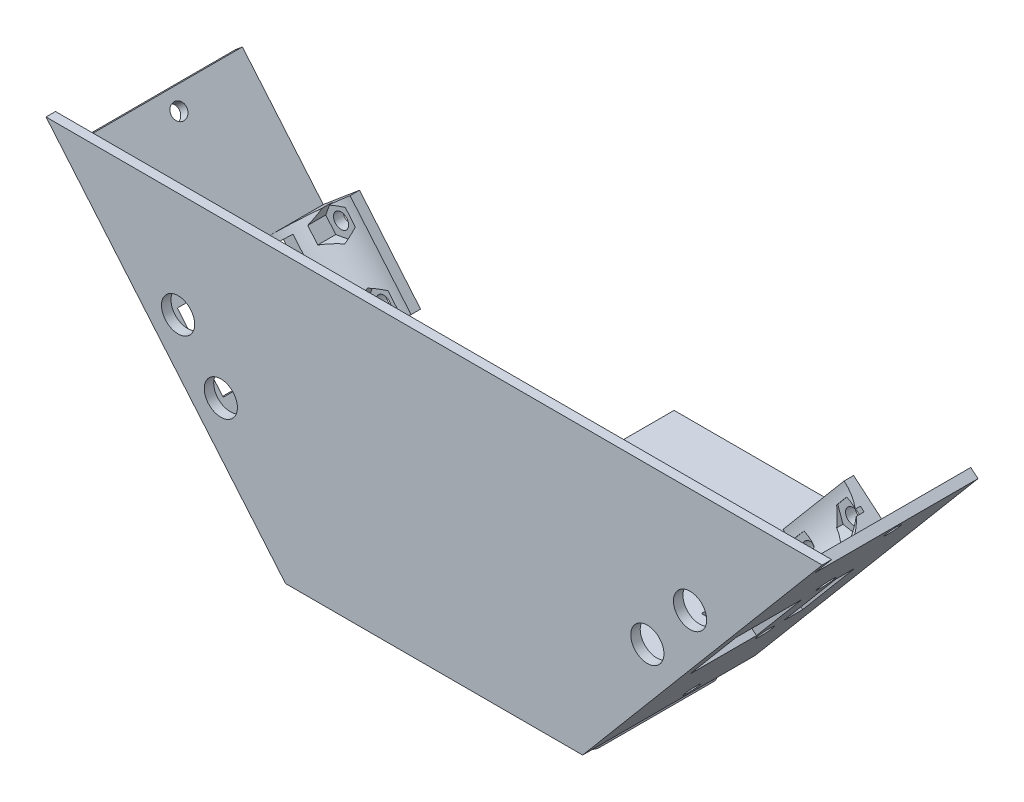
SolidWorks part; units mm, degrees
ref_plane "Front Plane" through (0, 0, 0) normal (0, 0, 1) x (1, 0, 0)
ref_plane "Top Plane" through (0, 0, 0) normal (0, 1, 0) x (1, 0, 0)
ref_plane "Right Plane" through (0, 0, 0) normal (1, 0, 0) x (0, 0, -1)
sketch "Sketch1" plane through (0, 0, 0) normal (0, 0, 1) x (1, 0, 0)
  line L0 (31.35, -1) -> (78.3808, 54.8311)
  line L1 (-31.35, -1) -> (31.35, -1)
  line L3 (-30.4197, 1) -> (30.4197, 1)
  line L5 (0, 0) -> (0, 17.9278) construction
  line L6 (-76.8512, 56.1196) -> (-30.4197, 1)
  line L7 (78.3808, 54.8311) -> (76.8512, 56.1196)
  line L8 (76.8512, 56.1196) -> (30.4197, 1)
  line L9 (-78.3808, 54.8311) -> (-76.8512, 56.1196)
  line L10 (30.4197, 1) -> (-30.4197, 1)
  line L11 (-31.35, -1) -> (-78.3808, 54.8311)
  point P0 (0, 0)
  dimension "D1" = 62.7
  dimension "D2" = 73
  dimension "D3" = 130.11
  dimension "D4" = 2
extrude "Boss-Extrude1" add sketch "Sketch1" along normal blind 31.4 contours L11 L1 L0 L7 L8 L10 L3 L6 L9 region at (0, 0.6684, 0)
sketch "Sketch2" plane through (0, 0, 0) normal (0, 0, -1) x (-1, 0, 0)
  line L0 (46.8932, 20.556) -> (39.2451, 26.9985)
  line L1 (76.8512, 56.1196) -> (30.4197, 1) construction
  line L2 (39.2451, 26.9985) -> (52.1302, 42.2947)
  line L3 (52.1302, 42.2947) -> (59.7783, 35.8521)
  line L4 (59.7783, 35.8521) -> (46.8932, 20.556)
  line L5 (78.3808, 54.8311) -> (76.8512, 56.1196) construction
  line L6 (0, 1) -> (0, 26.9985) construction
  line L7 (30.4197, 1) -> (-30.4197, 1) construction
  line L8 (-52.1302, 42.2947) -> (-59.7783, 35.8521)
  line L9 (-39.2451, 26.9985) -> (-52.1302, 42.2947)
  line L10 (-46.8932, 20.556) -> (-39.2451, 26.9985)
  line L11 (-59.7783, 35.8521) -> (-46.8932, 20.556)
  circle A0 centre (54.0215, 36.779) radius 1.6
  circle A1 centre (45.0019, 26.0717) radius 1.6014
  circle A2 centre (-45.0019, 26.0717) radius 1.6014
  circle A3 centre (-54.0215, 36.779) radius 1.6
  dimension "D4" = 3.2
  dimension "D5" = 3.2027
  dimension "D1" = 26.5
  dimension "D2" = 20
  dimension "D3" = 10
  dimension "D6" = 14
  dimension "D7" = 3
extrude "Boss-Extrude2" add sketch "Sketch2" against normal blind 2
fillet "Fillet1" radius 10 2 edges at (-53.3358, 28.204, 2) (53.3358, 28.204, 2)
sketch "Sketch3" plane through (0, 0, 0) normal (0, 0, -1) x (-1, 0, 0)
  line L1 (-50.7817, 37.3567) -> (-52.9019, 39.8736)
  line L2 (-52.9019, 39.8736) -> (-56.1417, 39.2959)
  line L3 (-56.1417, 39.2959) -> (-57.2613, 36.2013)
  line L4 (-57.2613, 36.2013) -> (-55.1411, 33.6844)
  line L5 (-55.1411, 33.6844) -> (-51.9013, 34.2621)
  line L6 (-51.9013, 34.2621) -> (-50.7817, 37.3567)
  line L7 (0, 0) -> (0, 47.8855) construction
  line L8 (-42.8817, 23.5548) -> (-41.7621, 26.6493)
  line L9 (-41.7621, 26.6493) -> (-43.8823, 29.1663)
  line L10 (-43.8823, 29.1663) -> (-47.1221, 28.5886)
  line L11 (-47.1221, 28.5886) -> (-48.2417, 25.494)
  line L12 (-48.2417, 25.494) -> (-46.1215, 22.9771)
  line L13 (-46.1215, 22.9771) -> (-42.8817, 23.5548)
  line L14 (46.1215, 22.9771) -> (42.8817, 23.5548)
  line L15 (48.2417, 25.494) -> (46.1215, 22.9771)
  line L16 (47.1221, 28.5886) -> (48.2417, 25.494)
  line L17 (43.8823, 29.1663) -> (47.1221, 28.5886)
  line L18 (41.7621, 26.6493) -> (43.8823, 29.1663)
  line L19 (42.8817, 23.5548) -> (41.7621, 26.6493)
  line L20 (51.9013, 34.2621) -> (50.7817, 37.3567)
  line L21 (55.1411, 33.6844) -> (51.9013, 34.2621)
  line L22 (57.2613, 36.2013) -> (55.1411, 33.6844)
  line L23 (56.1417, 39.2959) -> (57.2613, 36.2013)
  line L24 (52.9019, 39.8736) -> (56.1417, 39.2959)
  line L25 (50.7817, 37.3567) -> (52.9019, 39.8736)
  line L26 (-39.2451, 26.9985) -> (-52.1302, 42.2947) construction
  circle A0 centre (-54.0215, 36.779) radius 2.85 construction
  circle A1 centre (-45.0019, 26.0717) radius 2.85 construction
  dimension "D1" = 5.7
  dimension "D2" = 5.7
extrude "Cut-Extrude1" cut sketch "Sketch3" against normal blind 12 from offset 2 offset against normal yes
sketch "Sketch4" plane through (18.8304, -15.8623, 0) normal (0.7648, -0.6443, 0) x (0, 0, -1)
  line L0 (-31.4, 92.4327) -> (0, 92.4327) construction
  circle A0 centre (-15.7, 88.8327) radius 1.6
  circle A1 centre (-15.7, 23.0327) radius 1.6
  dimension "D1" = 3.2
  dimension "D3" = 3.2
  dimension "D2" = 65.8
  dimension "D4" = 3.6
extrude "Cut-Extrude2" cut sketch "Sketch4" against normal blind 2
mirror "Mirror1" about plane through (0, 0, 0) normal (1, 0, 0) of "Cut-Extrude2"
sketch "Sketch5" plane through (0, -1, 0) normal (0, -1, 0) x (1, 0, 0)
  line L0 (31.35, 31.4) -> (31.35, 0) construction
  line L1 (-24.25, 22.95) -> (-19.818, 22.95)
  line L2 (-24.25, 22.95) -> (-24.25, 8.45)
  line L3 (-24.25, 8.45) -> (-19.818, 8.45)
  line L4 (24.25, 22.95) -> (24.25, 8.45)
  line L5 (-24.25, 22.95) -> (-19.818, 21.625) construction
  line L6 (19.954, 22.95) -> (24.25, 22.95)
  line L7 (19.818, 26.15) -> (19.954, 26.15)
  line L8 (-19.818, 27.65) -> (-6, 27.65)
  line L9 (-19.818, 27.65) -> (-19.818, 22.95)
  line L10 (-19.818, 3.75) -> (19.818, 3.75)
  line L11 (19.818, 27.65) -> (19.818, 26.15)
  line L12 (6, 27.65) -> (19.818, 27.65)
  line L13 (-19.818, 3.75) -> (-12.0235, 8.45) construction
  line L14 (19.954, 26.15) -> (19.954, 22.95)
  line L15 (6, 27.65) -> (6, 29.65)
  line L16 (-26.25, 29.65) -> (-6, 29.65)
  line L17 (-26.25, 29.65) -> (-26.25, 1.75)
  line L18 (-26.25, 1.75) -> (26.25, 1.75)
  line L19 (26.25, 29.65) -> (26.25, 1.75)
  line L20 (-26.25, 29.65) -> (-19.818, 26.2319) construction
  line L21 (-26.25, 1.75) -> (-19.818, 5.1681) construction
  line L22 (-6, 27.65) -> (-6, 29.65)
  line L23 (-19.818, 8.45) -> (-19.818, 3.75)
  line L24 (6, 29.65) -> (26.25, 29.65)
  line L26 (19.818, 5.1681) -> (26.25, 1.75) construction
  line L28 (12.0235, 22.95) -> (19.818, 27.65) construction
  line L29 (13.6425, 22.95) -> (26.25, 29.65) construction
  line L31 (19.818, 8.45) -> (24.25, 8.45)
  line L32 (19.818, 8.45) -> (19.818, 3.75)
  point P0 (0, 15.7)
  point P10 (31.35, 15.7)
  point P11 (0, 15.7)
  point P16 (0, 15.7)
  dimension "D1" = 48.5
  dimension "D2" = 14.5
  dimension "D3" = 39.636
  dimension "D4" = 23.9
  dimension "D5" = 1.5
  dimension "D6" = 0.136
  dimension "D7" = 2
  dimension "D8" = 2
  dimension "D10" = 12
extrude "Boss-Extrude3" add sketch "Sketch5" along normal blind 4.9
sketch "Sketch6" plane through (0, -5.9, 0) normal (0, -1, 0) x (1, 0, 0)
  line L0 (-6, 29.65) -> (-26.25, 29.65)
  line L1 (-26.25, 29.65) -> (-26.25, 1.75)
  line L2 (-26.25, 1.75) -> (26.25, 1.75)
  line L3 (26.25, 1.75) -> (26.25, 29.65)
  line L4 (26.25, 29.65) -> (6, 29.65)
  line L5 (6, 29.65) -> (6, 27.65)
  line L6 (6, 27.65) -> (24.25, 27.65)
  line L7 (24.25, 27.65) -> (24.25, 3.75)
  line L8 (24.25, 3.75) -> (-24.25, 3.75)
  line L9 (-24.25, 3.75) -> (-24.25, 27.65)
  line L10 (-24.25, 27.65) -> (-6, 27.65)
  line L11 (-19.818, 27.65) -> (-6, 27.65) construction
  line L12 (-19.818, 27.65) -> (-6, 27.65) construction
  line L13 (-6, 27.65) -> (-6, 29.65)
extrude "Boss-Extrude4" add sketch "Sketch6" along normal blind 0.6
fillet "Fillet2" radius 2 4 edges at (26.25, -3.75, 29.65) (26.25, -3.75, 1.75) (-26.25, -3.75, 1.75) (-26.25, -3.75, 29.65)
fillet "Fillet3" radius 4 8 edges at (-15.125, -1, 29.65) (-25.6642, -1, 29.0642) (-26.25, -1, 15.7) (-25.6642, -1, 2.3358) (15.125, -1, 29.65) (25.6642, -1, 29.0642) (26.25, -1, 15.7) (25.6642, -1, 2.3358)
sketch "Sketch7" plane through (0, -6.5, 0) normal (0, -1, 0) x (1, 0, 0)
  line L0 (-24.25, 8.45) -> (-24.25, 22.95) construction
  line L1 (-18.25, 13.8577) -> (-30.25, 13.8577)
  line L2 (-18.25, 13.8577) -> (-18.25, 17.5423)
  line L3 (-18.25, 17.5423) -> (-30.25, 17.5423)
  line L4 (-30.25, 13.8577) -> (-30.25, 17.5423)
  line L5 (-18.25, 13.8577) -> (-30.25, 17.5423) construction
  line L6 (-18.25, 17.5423) -> (-30.25, 13.8577) construction
  line L7 (-30.25, 3.75) -> (-30.25, 27.65) construction
  point P0 (-24.25, 15.7)
extrude "Cut-Extrude3" cut sketch "Sketch7" against normal blind 2
sketch "Sketch8" plane through (0, 0, 0) normal (0, 0, -1) x (-1, 0, 0)
  line L0 (30.4197, 1) -> (-30.4197, 1) construction
  line L1 (-20, -1) -> (20, -1)
  line L2 (-20, -1) -> (-20, 1)
  line L3 (-20, 1) -> (20, 1)
  line L4 (20, -1) -> (20, 1)
  line L5 (-20, -1) -> (20, 1) construction
  line L6 (-20, 1) -> (20, -1) construction
  point P0 (0, 0)
  dimension "D1" = 40
extrude "Boss-Extrude5" add sketch "Sketch8" along normal blind 40
sketch "Sketch9" plane through (0, -1, 0) normal (0, -1, 0) x (1, 0, 0)
  line L0 (20, -40) -> (-20, -40) construction
  line L1 (-12.75, -7.75) -> (12.75, -7.75)
  line L2 (-12.75, -7.75) -> (-12.75, -32.25)
  line L3 (-12.75, -32.25) -> (12.75, -32.25)
  line L4 (12.75, -7.75) -> (12.75, -32.25)
  line L5 (-12.75, -7.75) -> (12.75, -32.25) construction
  line L6 (-12.75, -32.25) -> (12.75, -7.75) construction
  line L7 (-20, -40) -> (-20, 0) construction
  line L8 (-14.75, -5.75) -> (-14.75, -34.25)
  line L9 (-14.75, -34.25) -> (14.75, -34.25)
  line L10 (14.75, -5.75) -> (14.75, -34.25)
  line L11 (-14.75, -5.75) -> (14.75, -5.75)
  line L12 (-12.75, -11.5) -> (9.4027, -11.5) construction
  line L13 (0, -20) -> (29.1321, -20) construction
  circle A8 centre (10.5, -17.75) radius 1.1
  circle A9 centre (10.5, -17.75) radius 2.1
  circle A10 centre (-10.5, -17.75) radius 1.1
  circle A11 centre (-10.5, -17.75) radius 2.1
  circle A12 centre (-10.5, -29.75) radius 1.1
  circle A13 centre (-10.5, -29.75) radius 2.1
  circle A14 centre (10.5, -29.75) radius 1.1
  circle A15 centre (10.5, -29.75) radius 2.1
  point P0 (0, -20)
  point P8 (0, -40)
  point P10 (-20, -20)
  dimension "D5" = 2.25
  dimension "D7" = 2.2
  dimension "D8" = 2.2
  dimension "D1" = 25.5
  dimension "D2" = 24.5
  dimension "D4" = 2.5
  dimension "D6" = 2.25
  dimension "D9" = 12
  dimension "D3" = 2
extrude "Boss-Extrude6" add sketch "Sketch9" along normal blind 4 contours L11 L8 L9 L10 L1 L4 L3 L2 region at (0, -1, -6.1602)
extrude "Boss-Extrude7" add sketch "Sketch9<3>" along normal blind 2.5 contours A15 A14 | A9 A8 | A11 A10 | A13 A12 region at (8.4594, -1, -17.75) region at (-12.5406, -1, -17.75) region at (-12.5406, -1, -29.75) region at (8.4594, -1, -29.75)
sketch "Sketch9<3>" plane through (0, -1, 0) normal (0, -1, 0) x (1, 0, 0) same geometry as "Sketch9"
sketch "Sketch10" plane through (0, -5, 0) normal (0, -1, 0) x (1, 0, 0)
  line L1 (-10, 1.25) -> (10, 1.25)
  line L2 (-10, 1.25) -> (-10, -1.25)
  line L3 (-10, -1.25) -> (10, -1.25)
  line L4 (10, 1.25) -> (10, -1.25)
  line L5 (-10, 1.25) -> (10, -1.25) construction
  line L6 (-10, -1.25) -> (10, 1.25) construction
  point P0 (0, 0)
  dimension "D1" = 2.5
  dimension "D2" = 20
extrude "Cut-Extrude4" cut sketch "Sketch10" against normal blind 31
sketch "Sketch11" plane through (0, -5, 0) normal (0, -1, 0) x (1, 0, 0)
  line L0 (-12.75, -7.75) -> (12.75, -7.75) construction
  line L1 (-10, -1.25) -> (10, -1.25)
  line L2 (-10, -1.25) -> (-10, -7.75)
  line L3 (-10, -7.75) -> (10, -7.75)
  line L4 (10, -1.25) -> (10, -7.75)
extrude "Cut-Extrude5" cut sketch "Sketch11" against normal blind 31
sketch "Sketch12" plane through (0, -1, 0) normal (0, -1, 0) x (1, 0, 0)
  line L0 (20, -40) -> (20, 0) construction
  line L1 (-20, -40) -> (20, -40)
  line L2 (-20, -40) -> (-20, -34.25)
  line L3 (-20, -34.25) -> (20, -34.25)
  line L4 (20, -40) -> (20, -34.25)
extrude "Cut-Extrude6" cut sketch "Sketch12" against normal blind 31
sketch "Sketch13" plane through (0, 0, 31.4) normal (0, 0, 1) x (1, 0, 0)
  line L0 (31.35, 59) -> (81.8926, 59)
  line L1 (-31.35, -1) -> (31.35, -1)
  line L3 (-31.35, 59) -> (31.35, 59)
  line L5 (81.8926, 59) -> (31.35, -1)
  line L6 (31.35, -1) -> (78.3808, 54.8311) construction
  line L7 (0, 0) -> (0, 25.8031) construction
  line L8 (-31.35, 59) -> (-81.8926, 59)
  line L9 (-81.8926, 59) -> (-31.35, -1)
  dimension "D1" = 60
extrude "Boss-Extrude8" add sketch "Sketch13" along normal blind 2 from offset 3
sketch "Sketch14" plane through (0, 0, 36.4) normal (0, 0, 1) x (1, 0, 0)
  circle A0 centre (54.0215, 36.779) radius 3.5
  circle A1 centre (45.0019, 26.0717) radius 3.5
  circle A2 centre (-54.0215, 36.779) radius 3.5
  circle A3 centre (-45.0019, 26.0717) radius 3.5
  dimension "D1" = 7
  dimension "D2" = 7
  dimension "D3" = 7
  dimension "D4" = 7
extrude "Cut-Extrude7" cut sketch "Sketch14" against normal blind 10
sketch "Sketch16" plane through (0, 0, 31.4) normal (0, 0, 1) x (1, 0, 0)
  line L0 (78.3808, 54.8311) -> (76.8512, 56.1196)
  line L1 (76.8512, 56.1196) -> (30.4197, 1)
  line L2 (30.4197, 1) -> (-30.4197, 1)
  line L3 (-30.4197, 1) -> (-76.8512, 56.1196)
  line L4 (-76.8512, 56.1196) -> (-78.3808, 54.8311)
  line L5 (-78.3808, 54.8311) -> (-31.35, -1)
  line L6 (-31.35, -1) -> (31.35, -1)
  line L7 (31.35, -1) -> (78.3808, 54.8311)
extrude "Boss-Extrude9" add sketch "Sketch16" along normal blind 3
combine bodies "Combine1" operation type add bodies to combine 116 117
other "Move Face1" flip direction yes face at (-19.818, -3.45, 6.1) face at (-22.034, -3.45, 8.45) face at (-24.25, -5.05, 15.7) face at (-22.034, -3.45, 22.95) face at (-19.818, -3.45, 25.3) face at (-16.6893, -4.4667, 27.65) face at (16.6893, -4.4667, 27.65) face at (19.818, -3.45, 26.9) face at (19.954, -3.45, 24.55) face at (22.102, -3.45, 22.95) face at (24.25, -4.825, 15.7) face at (22.034, -3.45, 8.45) face at (19.818, -3.45, 6.1) face at (0, -4.825, 3.75) offset 0.05 parameters "D1"=0.05
sketch "Sketch17" plane through (0, -1, 0) normal (0, -1, 0) x (1, 0, 0)
  line L0 (-6, 27.7) -> (-6, 31.4) construction
  line L1 (-6, 17.6293) -> (6, 17.6293)
  line L2 (-6, 17.6293) -> (-6, 28.8887)
  line L3 (-6, 28.8887) -> (6, 28.8887)
  line L4 (6, 17.6293) -> (6, 28.8887)
  line L5 (-6, 17.6293) -> (6, 28.8887) construction
  line L6 (-6, 28.8887) -> (6, 17.6293) construction
  point P0 (0, 23.259)
extrude "Cut-Extrude8" cut sketch "Sketch17" against normal blind 10
sketch "Sketch18" plane through (-18.8304, -15.8623, 0) normal (-0.7648, -0.6443, 0) x (0, 0, 1)
  line L0 (36.4, 97.8836) -> (36.4, 19.4327) construction
  line L1 (32.4, 48.4327) -> (18.4, 48.4327)
  line L2 (32.4, 48.4327) -> (32.4, 63.4327)
  line L3 (32.4, 63.4327) -> (18.4, 63.4327)
  line L4 (18.4, 48.4327) -> (18.4, 63.4327)
  line L5 (32.4, 48.4327) -> (18.4, 63.4327) construction
  line L6 (32.4, 63.4327) -> (18.4, 48.4327) construction
  line L10 (0, 19.4327) -> (0, 92.4327) construction
  point P0 (25.4, 55.9327)
  point P8 (0, 55.9327)
  dimension "D1" = 4
  dimension "D2" = 15
  dimension "D3" = 14
extrude "Cut-Extrude9" cut sketch "Sketch18" against normal blind 10
mirror "Mirror2" about plane through (0, 0, 0) normal (1, 0, 0) of "Cut-Extrude9"
sketch "Sketch19" plane through (-18.8304, -15.8623, 0) normal (-0.7648, -0.6443, 0) x (0, 0, 1)
  line L0 (0, 55.9327) -> (44.397, 55.9327) construction
  line L1 (0, 19.4327) -> (0, 92.4327) construction
  line L7 (8, 47.4327) -> (12, 47.4327)
  line L8 (8, 47.4327) -> (8, 64.4327)
  line L9 (8, 64.4327) -> (12, 64.4327)
  line L10 (12, 47.4327) -> (12, 64.4327)
  line L11 (8, 47.4327) -> (12, 64.4327) construction
  line L12 (8, 64.4327) -> (12, 47.4327) construction
  circle A0 centre (15, 45.9327) radius 1.75
  circle A1 centre (15, 65.9327) radius 1.75
  point P6 (10, 55.9327)
  point P12 (0, 0)
  dimension "D1" = 3.5
  dimension "D2" = 10
  dimension "D3" = 15
  dimension "D4" = 4
  dimension "D5" = 17
  dimension "D6" = 10
extrude "Cut-Extrude10" cut sketch "Sketch19" against normal blind 10
mirror "Mirror3" about plane through (0, 0, 0) normal (1, 0, 0) of "Cut-Extrude10"
